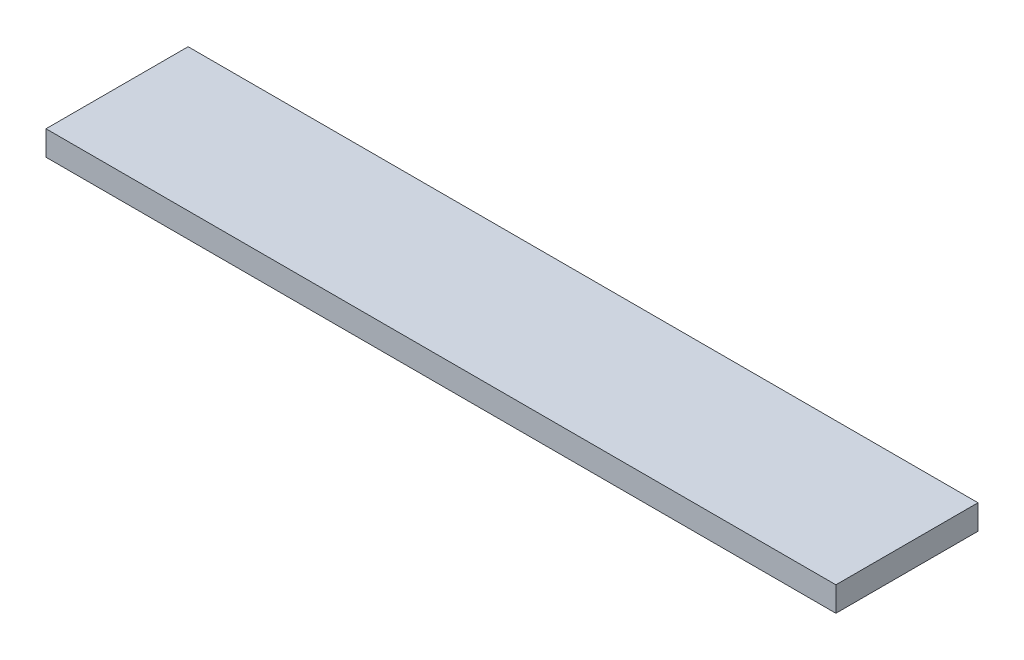
SolidWorks part; units mm, degrees
ref_plane "Front Plane" through (0, 0, 0) normal (0, 0, 1) x (1, 0, 0)
ref_plane "Top Plane" through (0, 0, 0) normal (0, 1, 0) x (1, 0, 0)
ref_plane "Right Plane" through (0, 0, 0) normal (1, 0, 0) x (0, 0, -1)
sketch "Sketch1" plane through (0, 0, 0) normal (0, 1, 0) x (1, 0, 0)
  line L1 (-35.3879, -3.6558) -> (5.2521, -3.6558)
  line L2 (-35.3879, -3.6558) -> (-35.3879, 3.6558)
  line L3 (-35.3879, 3.6558) -> (5.2521, 3.6558)
  line L4 (5.2521, -3.6558) -> (5.2521, 3.6558)
  line L5 (-35.3879, -3.6558) -> (5.2521, 3.6558) construction
  line L6 (-35.3879, 3.6558) -> (5.2521, -3.6558) construction
  point P0 (-15.0679, 0)
  dimension "D1" = 40.64
  dimension "D2" = 7.3115
extrude "Boss-Extrude1" add sketch "Sketch1" along normal blind 1.27 contours L3 L4 L1 L2
ref_axis "Axis1" through (5.2521, 0, 0) along (-1, 0, 0)
